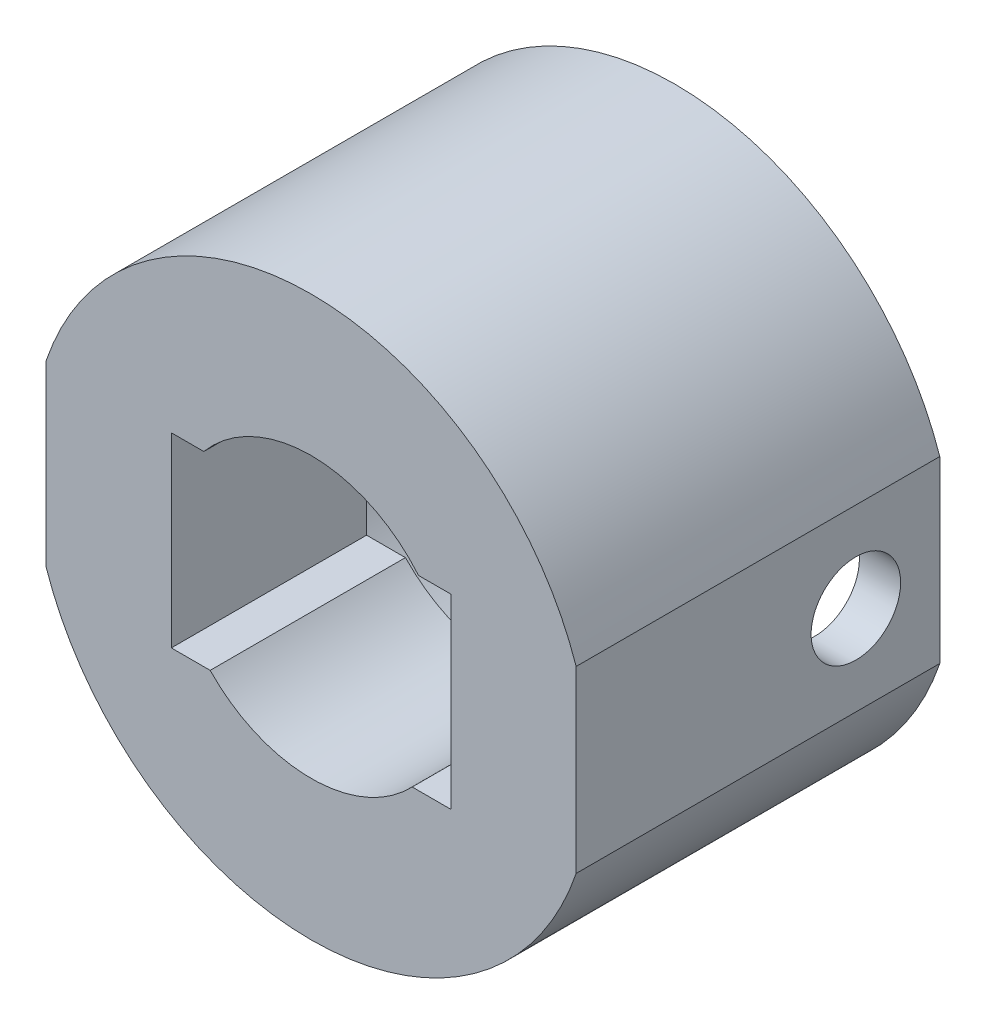
SolidWorks part; units mm, degrees
ref_plane "前视基准面" through (0, 0, 0) normal (0, 0, 1) x (1, 0, 0)
ref_plane "上视基准面" through (0, 0, 0) normal (0, 1, 0) x (1, 0, 0)
ref_plane "右视基准面" through (0, 0, 0) normal (1, 0, 0) x (0, 0, -1)
other "Configuration Table"
sketch "草图4" plane through (0, 0, 0) normal (0, 0, 1) x (1, 0, 0)
  line L0 (-7.3303, 3.2041) -> (-9.4728, 3.2041)
  line L1 (-9.4728, 3.2041) -> (-9.4728, -3.2041)
  line L2 (-9.4728, -3.2041) -> (-7.3303, -3.2041)
  line L3 (7.3303, 3.2041) -> (9.4728, 3.2041)
  line L4 (9.4728, 3.2041) -> (9.4728, -3.2041)
  line L5 (9.4728, -3.2041) -> (7.3303, -3.2041)
  circle A0 centre (0, 0) radius 8
  circle A1 centre (0, 0) radius 10
extrude "凸台-拉伸2" add sketch "草图4" along normal blind 10 contours L3 A1 L0 A0 | A0 L5 L4 L3 | L2 A1 L5 A0 | A0 L0 L1 L2 region at (-8.6151, 0, 0) region at (-8.4015, 3.4054, 0) region at (8.6151, 0, 0) region at (0, -8.2013, 0)
sketch "草图5" plane through (-9.4728, 0, 0) normal (-1, 0, 0) x (0, 0, 1)
  line L0 (0, 0) -> (3, 0)
  circle A0 centre (3, 0) radius 1.6
extrude "切除-拉伸1" cut sketch "草图5" against normal blind 27 contours A0 region at (-9.4728, -1.5547, 3)
sketch "草图8" plane through (0, 0, 0) normal (0, 0, -1) x (-1, 0, 0)
  circle A0 centre (0, 0) radius 8
extrude "凸台-拉伸4" add sketch "草图8" against normal up to surface (10 mm away) up to face at (8, 0, 10)
extrude "切除-拉伸4" cut sketch "草图8<3>" against normal blind 4.62
sketch "草图8<3>" plane through (0, 0, 0) normal (0, 0, -1) x (-1, 0, 0) same geometry as "草图8"
sketch "草图10" plane through (0, 0, 10) normal (0, 0, 1) x (1, 0, 0)
  circle A0 centre (0, 0) radius 5
extrude "切除-拉伸6" cut sketch "草图10" against normal blind 33.62 contours A0
sketch "草图11" plane through (0, 0, 10) normal (0, 0, 1) x (1, 0, 0)
  line L0 (-9.4728, 3.2041) -> (-5, 3.2041)
  line L1 (-5, 3.2041) -> (-5, -3.4581)
  line L2 (-5, -3.4581) -> (5, -3.4581)
  line L3 (5, -3.4581) -> (5, 3.2041)
  line L4 (5, 3.2041) -> (-5, 3.2041)
  circle M1 centre (0, 0) radius 5
extrude "切除-拉伸7" cut sketch "草图11" against normal blind 33.62 contours L2 L3 M1 | L3 L4 M1 | L4 L1 M1 | L1 L2 M1 region at (-4.6598, 2.4229, 10) region at (-4.5956, -2.6194, 10) region at (4.6598, 2.4229, 10) region at (4.5956, -2.6194, 10)
sketch "草图13" plane through (0, 0, 4.62) normal (0, 0, -1) x (-1, 0, 0)
  line L0 (-5, -3.4581) -> (-3.6113, -3.4581) construction
  line L1 (3.6113, -3.4581) -> (5, -3.4581) construction
  line L2 (5, -3.4581) -> (5, 3.2041) construction
  line L3 (5, 3.2041) -> (3.8384, 3.2041) construction
  line L4 (-3.8384, 3.2041) -> (-5, 3.2041) construction
  line L5 (-5, 3.2041) -> (-5, -3.4581) construction
  line L6 (-5, -3.4581) -> (-3.6113, -3.4581)
  line L7 (3.6113, -3.4581) -> (5, -3.4581)
  line L8 (5, -3.4581) -> (5, 3.2041)
  line L9 (5, 3.2041) -> (3.8384, 3.2041)
  line L10 (-3.8384, 3.2041) -> (-5, 3.2041)
  line L11 (-5, 3.2041) -> (-5, -3.4581)
  circle A0 centre (0, 0) radius 8
  arc A1 (-3.6113, -3.4581) -> (3.6113, -3.4581) centre (0, 0) ccw construction
  arc A2 (3.8384, 3.2041) -> (-3.8384, 3.2041) centre (0, 0) ccw construction
  arc A3 (-3.6113, -3.4581) -> (3.6113, -3.4581) centre (0, 0) ccw
  arc A4 (3.8384, 3.2041) -> (-3.8384, 3.2041) centre (0, 0) ccw
sketch "草图14" plane through (0, 0, 10) normal (0, 0, 1) x (1, 0, 0)
  line L0 (-9.4728, 3.2041) -> (-9.4728, -3.2041)
  line L1 (9.4728, 3.2041) -> (9.4728, -3.2041)
  line L2 (-3.8384, 3.2041) -> (-5, 3.2041) construction
  line L3 (-5, 3.2041) -> (-5, -3.4581) construction
  line L4 (-5, -3.4581) -> (-3.6113, -3.4581) construction
  line L5 (3.6113, -3.4581) -> (5, -3.4581) construction
  line L6 (5, -3.4581) -> (5, 3.2041) construction
  line L7 (5, 3.2041) -> (3.8384, 3.2041) construction
  line L8 (-3.8384, 3.2041) -> (-5, 3.2041)
  line L9 (-5, 3.2041) -> (-5, -3.4581)
  line L10 (-5, -3.4581) -> (-3.6113, -3.4581)
  line L11 (3.6113, -3.4581) -> (5, -3.4581)
  line L12 (5, -3.4581) -> (5, 3.2041)
  line L13 (5, 3.2041) -> (3.8384, 3.2041)
  circle A0 centre (0, 0) radius 10
  arc A1 (-3.6113, -3.4581) -> (3.6113, -3.4581) centre (0, 0) ccw construction
  arc A2 (3.8384, 3.2041) -> (-3.8384, 3.2041) centre (0, 0) ccw construction
  arc A3 (-3.6113, -3.4581) -> (3.6113, -3.4581) centre (0, 0) ccw
  arc A4 (3.8384, 3.2041) -> (-3.8384, 3.2041) centre (0, 0) ccw
  arc M2 (-9.4728, -3.2041) -> (9.4728, -3.2041) centre (0, 0) ccw
  line M3 (9.4728, -3.2041) -> (9.4728, 3.2041)
  arc M4 (9.4728, 3.2041) -> (-9.4728, 3.2041) centre (0, 0) ccw
  line M5 (-9.4728, 3.2041) -> (-9.4728, -3.2041)
  line M6 (3.8384, 3.2041) -> (5, 3.2041)
  line M7 (5, 3.2041) -> (5, -3.4581)
  line M8 (5, -3.4581) -> (3.6113, -3.4581)
  arc M9 (3.6113, -3.4581) -> (-3.6113, -3.4581) centre (0, 0) cw
  line M10 (-3.6113, -3.4581) -> (-5, -3.4581)
  line M11 (-5, -3.4581) -> (-5, 3.2041)
  line M12 (-5, 3.2041) -> (-3.8384, 3.2041)
  arc M13 (-3.8384, 3.2041) -> (3.8384, 3.2041) centre (0, 0) cw
extrude "凸台-拉伸5" add sketch "草图14" along normal blind 3 contours M5 M2 M3 M4 M13 M6 M7 M8 M9 M10 M11 M12 region at (0, 9.7245, 10)
extrude "切除-拉伸8" cut sketch "草图13" against normal blind 1.4
sketch "草图15" plane through (0, 0, 0) normal (0, 0, -1) x (-1, 0, 0)
  line L0 (-9.4728, 3.2041) -> (-8, 3.2041)
  line L1 (-9.4728, 3.2041) -> (-9.4728, -3.2041) construction
  line L2 (-8, 3.2041) -> (-8, -3.2041)
  line L3 (-8, -3.2041) -> (8, -3.2041)
  line L4 (8, -3.2041) -> (8, 3.2041)
  line L5 (8, 3.2041) -> (-7.8883, 3.2041)
  line L6 (-7.8883, 3.2041) -> (-8, 3.2041)
  arc A0 (9.4728, 3.2041) -> (-9.4728, 3.2041) centre (0, 0) ccw construction
  circle M1 centre (0, 0) radius 8
extrude "切除-拉伸10" cut sketch "草图15" against normal up to surface (6.02 mm away) contours L5 L3 M1 | L2 L3 L4 L5 L6 region at (0, 0, 0) up to face at (0, -0.0952, 6.02)
